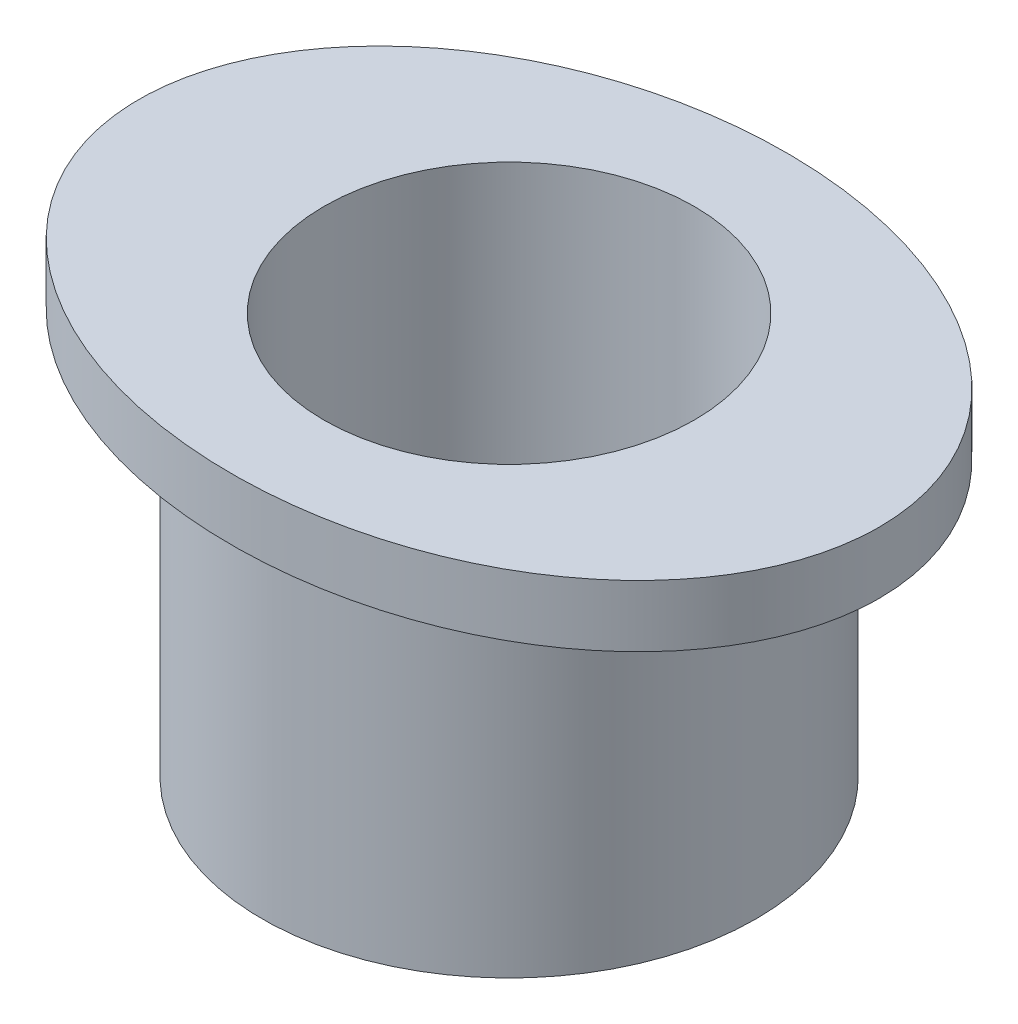
SolidWorks part; units mm, degrees
material "ABS"
ref_plane "Front Plane" through (0, 0, 0) normal (0, 0, 1) x (1, 0, 0)
ref_plane "Top Plane" through (0, 0, 0) normal (0, 1, 0) x (1, 0, 0)
ref_plane "Right Plane" through (0, 0, 0) normal (1, 0, 0) x (0, 0, -1)
sketch "Sketch1" plane through (0, 0, 0) normal (0, 1, 0) x (1, 0, 0)
  circle A0 centre (0, 0) radius 3
  dimension "D1" = 6
extrude "Extrude-Thin1" add sketch "Sketch1" against normal blind 5.5 thin thin type one direction wall 1
sketch "Sketch2" plane through (0, 0, 0) normal (0, 1, 0) x (1, 0, 0)
  line L0 (0, 4.5) -> (0, -4.5) construction
  line L1 (-6, 0) -> (6, 0) construction
  circle A0 centre (0, 0) radius 3
  circle A1 centre (0, 0) radius 3 construction
  ellipse E0 centre (0, 0) end of major axis (6, 0) minor radius 4.5
  dimension "D1" = 9
  dimension "D2" = 12
extrude "Boss-Extrude1" add sketch "Sketch2" along normal blind 1
